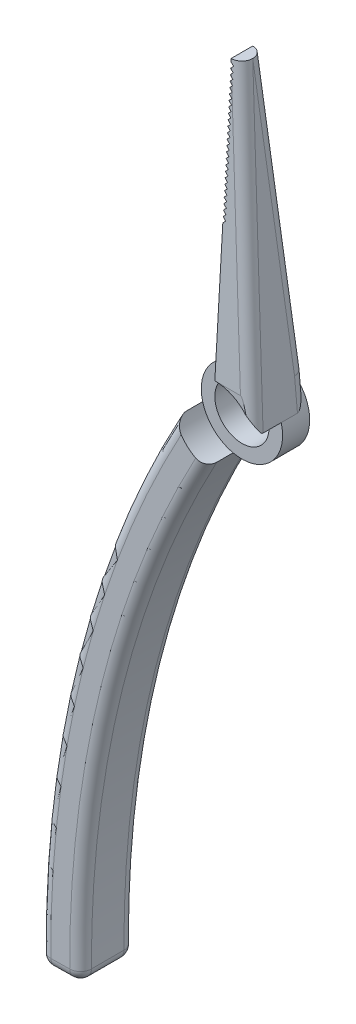
SolidWorks part; units mm, degrees
ref_plane "Front Plane" through (0, 0, 0) normal (0, 0, 1) x (1, 0, 0)
ref_plane "Top Plane" through (0, 0, 0) normal (0, 1, 0) x (1, 0, 0)
ref_plane "Right Plane" through (0, 0, 0) normal (1, 0, 0) x (0, 0, -1)
sketch "Sketch1" plane through (0, 0, 0) normal (0, 0, 1) x (1, 0, 0)
  line L0 (0, 7.5) -> (0, 57.5)
  line L1 (0, 57.5) -> (2, 57.5)
  line L2 (2, 57.5) -> (7.2444, 1.9411)
  line L3 (0, 0) -> (7.5, 0) construction
  circle A0 centre (0, 0) radius 7.5
  dimension "D1" = 15
  dimension "D2" = 50
  dimension "D3" = 15
  dimension "D4" = 2
extrude "Boss-Extrude1" add sketch "Sketch1" along normal mid plane 10 contours A0 L2 L1 L0 | A0 region at (2.5105, 27.1192, 0) region at (0, 0, 0)
sketch "Sketch2" plane through (0, 0, 5) normal (0, 0, 1) x (1, 0, 0)
  line L0 (-7.2444, -1.9411) -> (7.2444, 1.9411) construction
  arc A0 (-7.2444, -1.9411) -> (-32.2444, -101.9411) centre (167.731, -98.81) ccw
  point P6 (0, 0)
  dimension "D3" = 200
  dimension "D1" = 25
  dimension "D2" = 100
extrude "Extrude-Thin1" add sketch "Sketch2" against normal blind 10 thin thin type one direction reverse wall 7.5
sketch "Sketch3" plane through (0, 0, 5) normal (0, 0, 1) x (1, 0, 0)
  circle A0 centre (0, 0) radius 5
extrude "Cut-Extrude1" cut sketch "Sketch3" against normal blind 10
sketch "Sketch4" plane through (0, 0, 5) normal (0, 0, 1) x (1, 0, 0)
  circle A0 centre (0, 0) radius 7.5
extrude "Cut-Extrude2" cut sketch "Sketch4" against normal blind 5
sketch "Sketch5" plane through (0, 0, 0) normal (-1, 0, 0) x (0, 0, 1)
  line L0 (2, 57.5) -> (5, 7.5)
  line L1 (5, 57.5) -> (-5, 57.5) construction
  line L2 (2, 57.5) -> (7.8201, 57.5)
  line L3 (7.8201, 57.5) -> (7.8201, 7.5)
  line L4 (7.8201, 7.5) -> (5, 7.5)
  line L5 (0, 57.5) -> (0, 7.5) construction
  line L6 (-7.8201, 57.5) -> (-7.8201, 7.5)
  line L7 (-2, 57.5) -> (-7.8201, 57.5)
  line L8 (-2, 57.5) -> (-5, 7.5)
  line L9 (-7.8201, 7.5) -> (-5, 7.5)
  dimension "D1" = 2
extrude "Cut-Extrude9" cut sketch "Sketch5" against normal through all contours L3 L4 L0 L2
fillet "Fillet1" radius 2 10 edges at (4.3599, 32.5, 3.5) (4.6222, 29.7206, -5) (-28.4949, -101.8824, -5) (-28.4949, -101.8824, 5) (-24.7454, -101.8237, 0) (-32.2444, -101.9411, 0) (-19.2601, -53.0875, 5) (-19.2601, -53.0875, -5) (-26.2975, -50.3029, -5) (-26.2975, -50.3029, 5)
sketch "Sketch7" plane through (0, 0, 0) normal (0, 0, 1) x (1, 0, 0)
  line L0 (0, 32.5) -> (0.5, 32.5) construction
  line L1 (0, 57.5) -> (0, 7.5) construction
  line L2 (0, 32) -> (0.5, 32.5)
  line L3 (0.5, 32.5) -> (0, 33)
  dimension "D1" = 45
  dimension "D2" = 1
extrude "Cut-Extrude10" cut sketch "Sketch7" against normal through all and the other way through all
pattern_linear "LPattern1" count 25 spacing 1 along (0, 1, 0) of "Cut-Extrude10"
sketch "Sketch8" plane through (0, 0, 0) normal (-1, 0, 0) x (0, 0, 1)
  line L0 (0, 7.5) -> (0.0077, 57.5) construction
  line L5 (-7.6351, 7.5023) -> (-7.6197, 57.5023)
  line L6 (-5, 7.5015) -> (-7.6351, 7.5023)
  line L7 (-1.9846, 57.5006) -> (-5, 7.5015)
  line L8 (-7.6197, 57.5023) -> (-1.9846, 57.5006)
extrude "Cut-Extrude11" cut sketch "Sketch8" against normal through all
fillet "Fillet3" radius 2 3 edges at (2.3553, 7.5015, -5) (5.2143, 17.2147, -4.4142) (2.7946, 49.0822, -2.4923)
